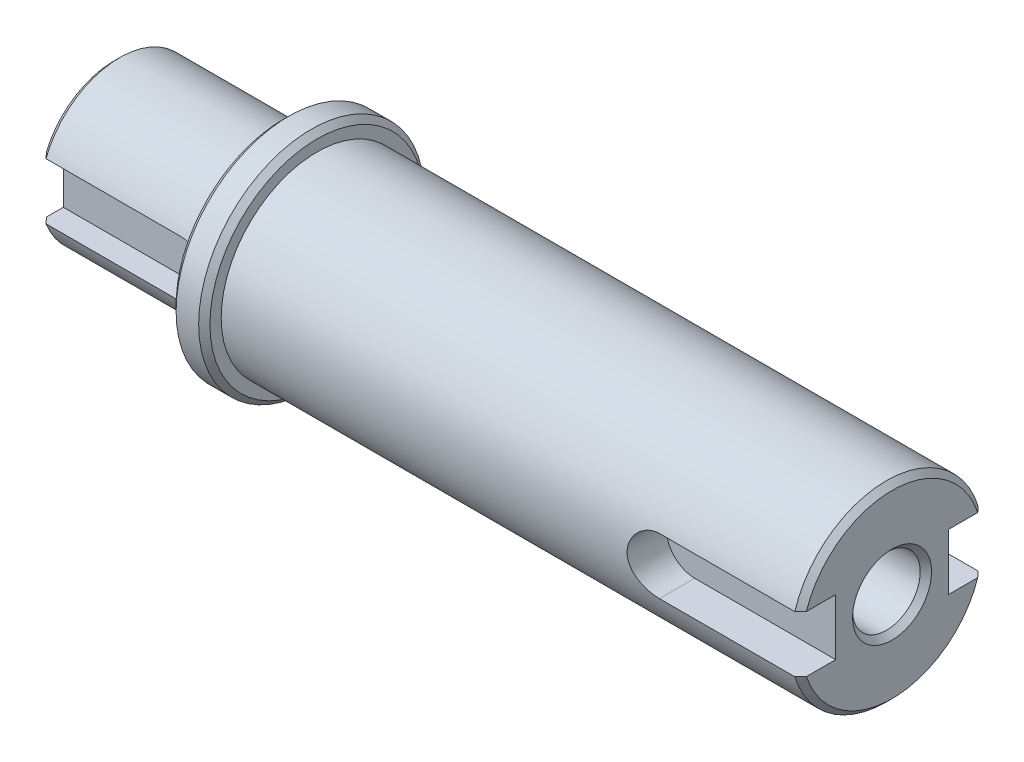
SolidWorks part; units mm, degrees
ref_plane "前视基准面" through (0, 0, 0) normal (0, 0, 1) x (1, 0, 0)
ref_plane "上视基准面" through (0, 0, 0) normal (0, 1, 0) x (1, 0, 0)
ref_plane "右视基准面" through (0, 0, 0) normal (1, 0, 0) x (0, 0, -1)
other "Configuration Table"
sketch "草图1" plane through (0, 0, 0) normal (0, 0, 1) x (1, 0, 0)
  line L0 (0, 0) -> (83.8798, 0) construction
  line L1 (0, 0) -> (0, 7)
  line L2 (0, 7) -> (15, 7)
  line L3 (15, 7) -> (15, 10)
  line L4 (15, 10) -> (18, 10)
  line L5 (18, 10) -> (18, 8.5)
  line L6 (18, 8.5) -> (69, 8.5)
  line L7 (69, 8.5) -> (69, 0)
  line L8 (69, 0) -> (0, 0)
  dimension "D1" = 20
  dimension "D2" = 14
  dimension "D3" = 17
  dimension "D4" = 15
  dimension "D5" = 18
  dimension "D6" = 51
revolve "旋转1" add sketch "草图1" angle 360 about L0
chamfer "倒角1" distance 0.5 angle 45 4 edges at (69, 0, 8.5) (18, 0, 10) (15, 0, 10) (0, 0, 7)
hole_wizard "M6 螺纹孔的螺纹孔钻头1" positions "草图2" profile "草图3" hole size "M6" standard "GB"
sketch "草图2" plane through (69, 0, 0) normal (1, 0, 0) x (0, 0, -1)
  point P0 (0, 0)
sketch "草图3" plane through (69, 0, 0) normal (0, 1, 0) x (0, 0, -1)
  line L0 (0, 0) -> (0, 16.8026)
  line L1 (0, 16.8026) -> (3, 15)
  line L2 (3, 15) -> (3, 0.5)
  line L3 (3, 0.5) -> (3.5, 0)
  line L5 (3.5, 0) -> (0, 0)
  line L6 (-3, 0.5) -> (-3.5, 0) construction
  line L10 (0, 16.8026) -> (-3, 15) construction
  line L11 (0, -6.35) -> (0, 107.95) construction
  dimension "孔直径" = 6
  dimension "孔深度" = 15
  dimension "近端锥形沉头孔直径" = 7
  dimension "近端锥形沉头孔角度" = 90
  dimension "导头角度" = 118
sketch "草图4" plane through (0, 0, 0) normal (0, 0, 1) x (1, 0, 0)
  line L0 (0, 2.5) -> (12.5, 2.5)
  line L1 (0, 6.5) -> (0, -6.5) construction
  line L2 (12.5, -2.5) -> (0, -2.5)
  line L3 (0, -2.5) -> (0, 2.5)
  arc A0 (12.5, 2.5) -> (12.5, -2.5) centre (12.5, 0) cw
  point P6 (0, 0)
  dimension "D1" = 5
  dimension "D2" = 12.5
extrude "切除-拉伸1" cut sketch "草图4" along normal blind 10 from offset 4.5
sketch "草图5" plane through (0, 0, 0) normal (0, 0, 1) x (1, 0, 0)
  line L0 (69, 2.5) -> (56.5, 2.5)
  line L1 (69, -8) -> (69, 8) construction
  line L2 (56.5, -2.5) -> (69, -2.5)
  line L3 (69, -2.5) -> (69, 2.5)
  line L4 (68.5, 0) -> (69, 0) construction
  arc A0 (56.5, 2.5) -> (56.5, -2.5) centre (56.5, 0) ccw
  point P9 (69, 0)
  dimension "D1" = 5
  dimension "D2" = 12.5
extrude "切除-拉伸2" cut sketch "草图5" along normal blind 10 from offset 5
pattern_circular "阵列(圆周)1" count 2 over 360 about axis through (0, 0, 0) along (-1, 0, 0) of "切除-拉伸2" reverse direction yes
